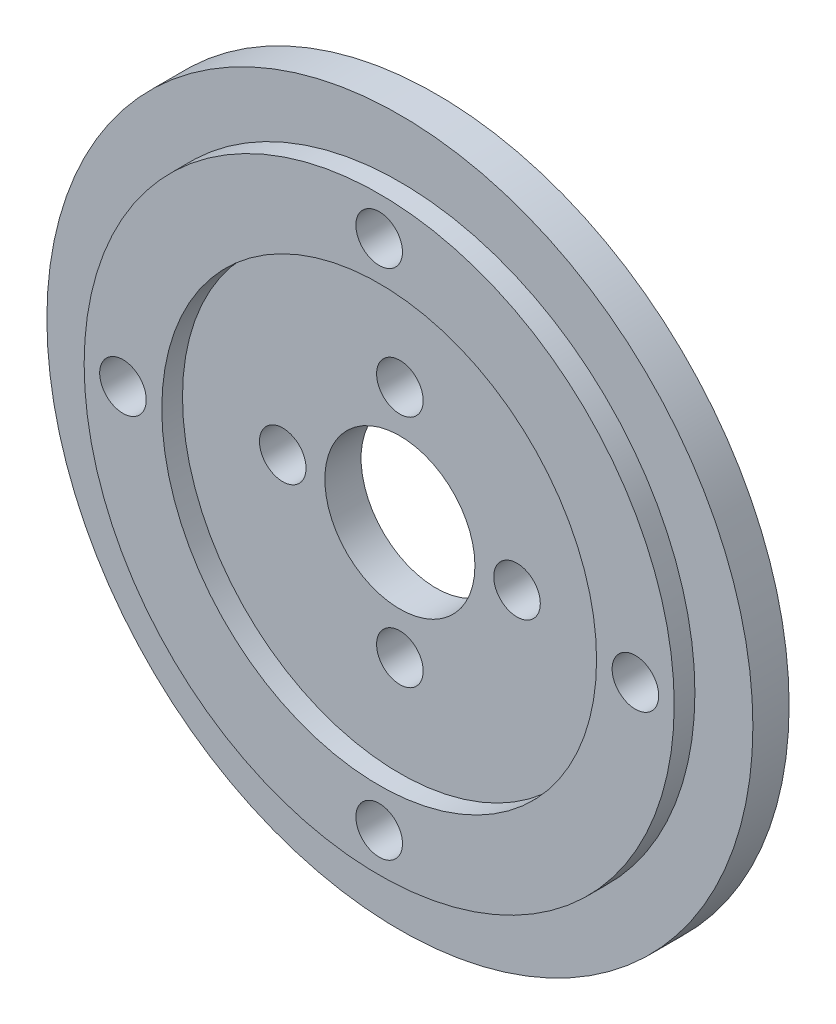
SolidWorks part; units mm, degrees
ref_plane "Front Plane" through (0, 0, 0) normal (0, 0, 1) x (1, 0, 0)
ref_plane "Top Plane" through (0, 0, 0) normal (0, 1, 0) x (1, 0, 0)
ref_plane "Right Plane" through (0, 0, 0) normal (1, 0, 0) x (0, 0, -1)
sketch "Sketch1" plane through (0, 0, 0) normal (0, 0, 1) x (1, 0, 0)
  circle A0 centre (0, 0) radius 34.1
  dimension "D1" = 68.2
extrude "Boss-Extrude1" add sketch "Sketch1" along normal mid plane 3.5
sketch "Sketch4" plane through (0, 0, 1.75) normal (0, 0, 1) x (1, 0, 0)
  circle A0 centre (0, 0) radius 28.5
  circle A1 centre (0, 0) radius 21
  dimension "D1" = 57
  dimension "D2" = 42
extrude "Boss-Extrude2" add sketch "Sketch4" along normal blind 2
sketch "Sketch3" plane through (0, 0, 1.75) normal (0, 0, 1) x (1, 0, 0)
  line L0 (0, 0) -> (0, 24.75) construction
  circle A0 centre (0, 24.75) radius 2.25
  circle A8 centre (0, 0) radius 11.3137 construction
  circle A9 centre (0, 11.3137) radius 2.25
  circle A10 centre (24.75, 0) radius 2.25
  circle A11 centre (11.3137, 0) radius 2.25
  circle A12 centre (0, -24.75) radius 2.25
  circle A13 centre (0, -11.3137) radius 2.25
  circle A14 centre (-24.75, 0) radius 2.25
  circle A15 centre (-11.3137, 0) radius 2.25
  point P21 (0, 0)
  dimension "D2" = 4.5
  dimension "D3" = 22.6274
  dimension "D4" = 4.5
  dimension "D5" = 4
  dimension "D1" = 24.75
extrude "Cut-Extrude2" cut sketch "Sketch3" against normal through all both and the other way through all
sketch "Sketch2" plane through (0, 0, 1.75) normal (0, 0, 1) x (1, 0, 0)
  circle A0 centre (0, 0) radius 7.25
  dimension "D1" = 14.5
extrude "Cut-Extrude1" cut sketch "Sketch2" against normal through all
